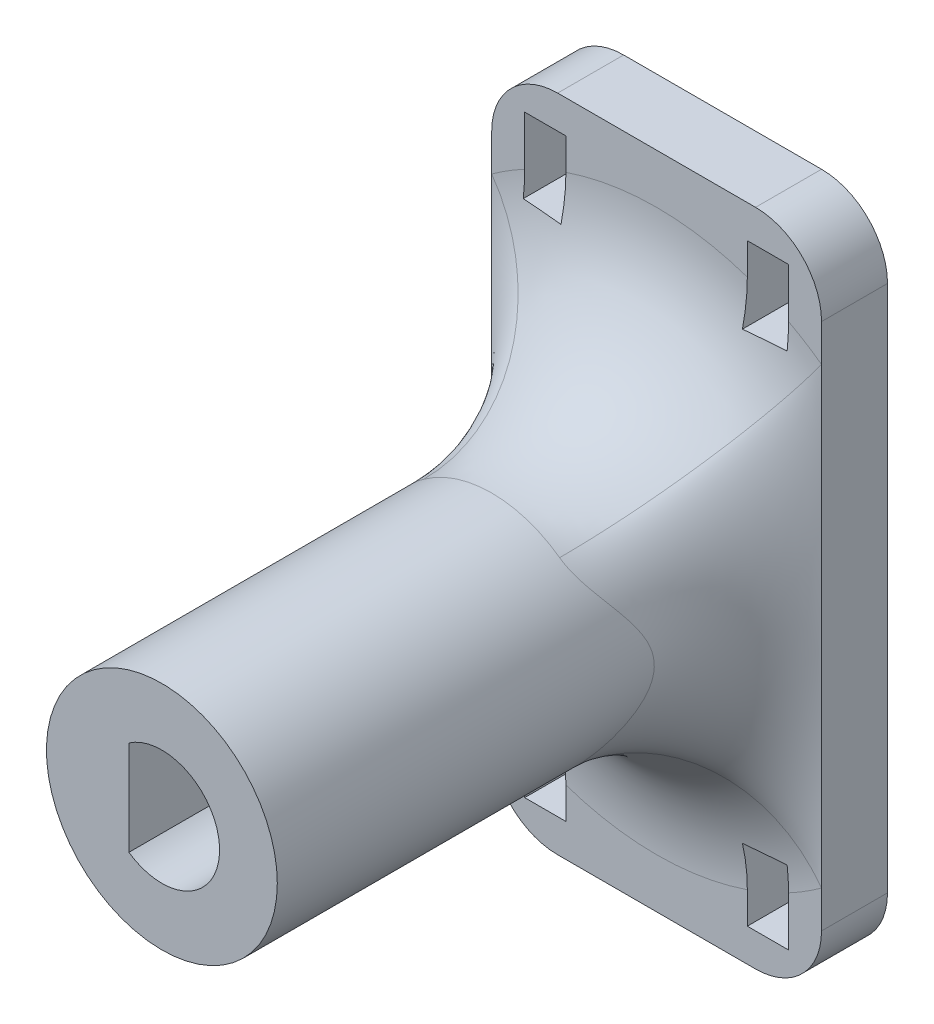
SolidWorks part; units mm, degrees
ref_plane "Front Plane" through (0, 0, 0) normal (0, 0, 1) x (1, 0, 0)
ref_plane "Top Plane" through (0, 0, 0) normal (0, 1, 0) x (1, 0, 0)
ref_plane "Right Plane" through (0, 0, 0) normal (1, 0, 0) x (0, 0, -1)
sketch "Sketch1" plane through (0, 0, 0) normal (0, 0, 1) x (1, 0, 0)
  circle A0 centre (0, 0) radius 3.5
  circle A1 centre (0, 0) radius 7
  dimension "D1" = 7
  dimension "D2" = 14
extrude "Boss-Extrude1" add sketch "Sketch1" along normal blind 12
sketch "Sketch2" plane through (0, 0, 0) normal (0, 0, -1) x (-1, 0, 0)
  line L1 (2, -4) -> (5, -4)
  line L2 (2, -4) -> (2, 4)
  line L3 (2, 4) -> (5, 4)
  line L4 (5, -4) -> (5, 4)
  dimension "D1" = 8
  dimension "D2" = 3
  dimension "D3" = 4
  dimension "D4" = 2
extrude "Boss-Extrude2" add sketch "Sketch2" against normal up to surface (12 mm away) up to face at (7, 0, 12)
sketch "Sketch3" plane through (0, 0, 0) normal (1, 0, 0) x (0, 0, -1)
  line L0 (-12, 7) -> (-12, -7) construction
  circle A0 centre (-6, 0) radius 1.25
  dimension "D1" = 2.5
  dimension "D2" = 6
extrude "Cut-Extrude1" cut sketch "Sketch3" against normal blind 12
sketch "Sketch4" plane through (0, 0, 0) normal (0, 0, -1) x (-1, 0, 0)
  line L1 (10, -20) -> (-10, -20)
  line L2 (10, -20) -> (10, 20)
  line L3 (10, 20) -> (-10, 20)
  line L4 (-10, -20) -> (-10, 20)
  line L5 (-8, -18) -> (-5.5, -18)
  line L6 (-8, -18) -> (-8, -13.5)
  line L7 (-8, -13.5) -> (-5.5, -13.5)
  line L8 (-5.5, -18) -> (-5.5, -13.5)
  line L9 (5.5, -18) -> (8, -18)
  line L10 (5.5, -18) -> (5.5, -13.5)
  line L11 (5.5, -13.5) -> (8, -13.5)
  line L12 (8, -18) -> (8, -13.5)
  line L13 (-8, 13.5) -> (-5.5, 13.5)
  line L14 (-8, 13.5) -> (-8, 18)
  line L15 (-8, 18) -> (-5.5, 18)
  line L16 (-5.5, 13.5) -> (-5.5, 18)
  line L17 (5.5, 13.5) -> (8, 13.5)
  line L18 (5.5, 13.5) -> (5.5, 18)
  line L19 (5.5, 18) -> (8, 18)
  line L20 (8, 13.5) -> (8, 18)
  dimension "D1" = 20
  dimension "D2" = 40
  dimension "D3" = 10
  dimension "D4" = 20
  dimension "D5" = 4.5
  dimension "D6" = 2.5
  dimension "D7" = 4.5
  dimension "D8" = 2.5
  dimension "D9" = 4.5
  dimension "D10" = 2.5
  dimension "D11" = 4.5
  dimension "D12" = 2.5
  dimension "D13" = 2
  dimension "D14" = 2
  dimension "D15" = 2
  dimension "D16" = 2
  dimension "D17" = 2
  dimension "D18" = 2
  dimension "D19" = 2
sketch "Sketch5" plane through (0, 0, 0) normal (0, 0, -1) x (-1, 0, 0)
  circle A0 centre (0, 0) radius 7
extrude "Boss-Extrude5" add sketch "Sketch5" along normal blind 18
extrude "Boss-Extrude6" add sketch "Sketch4" along normal blind 4 from offset 18
fillet "Fillet1" radius 10 1 edges at (-7, 0, -18)
fillet "Fillet2" radius 4 4 edges at (10, 20, -20) (-10, 20, -20) (10, -20, -20) (-10, -20, -20)
